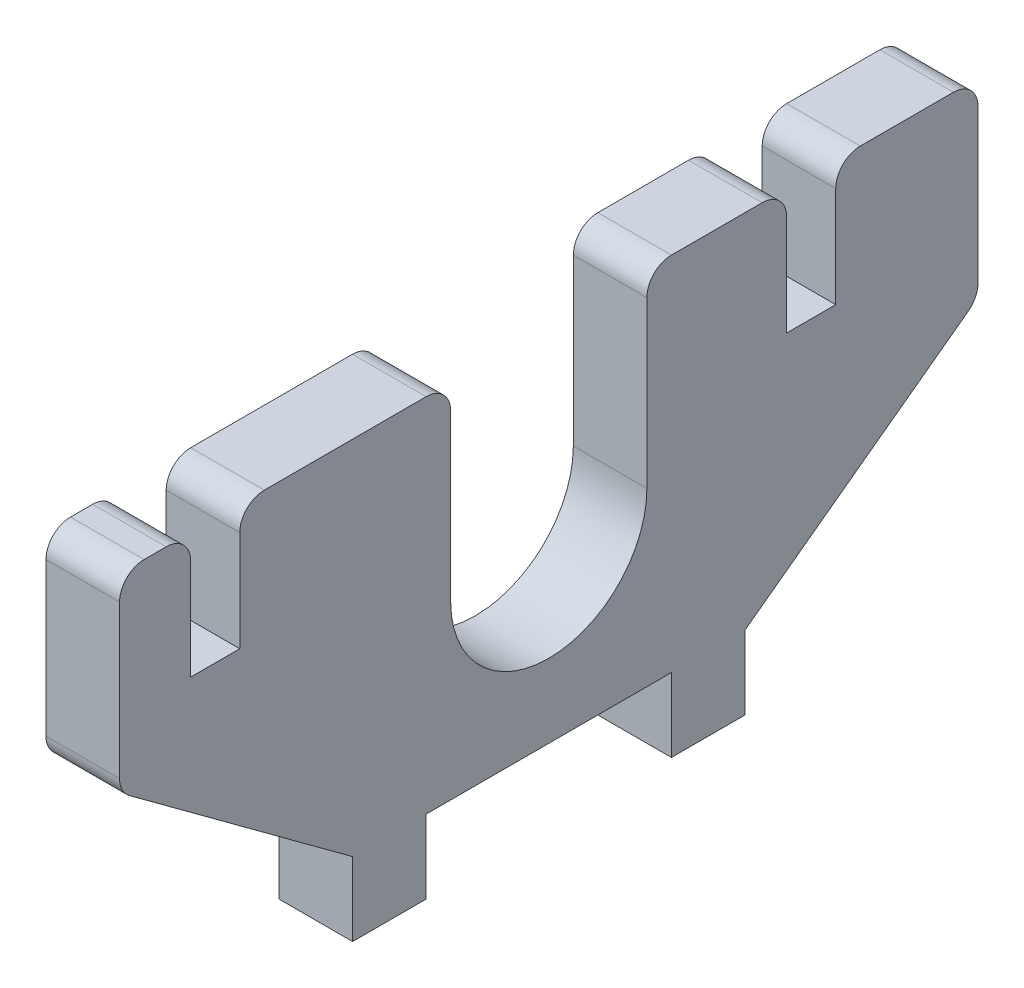
SolidWorks part; units mm, degrees
ref_plane "Front Plane" through (0, 0, 0) normal (0, 0, 1) x (1, 0, 0)
ref_plane "Top Plane" through (0, 0, 0) normal (0, 1, 0) x (1, 0, 0)
ref_plane "Right Plane" through (0, 0, 0) normal (1, 0, 0) x (0, 0, -1)
sketch "Sketch1" plane through (0, 0, 0) normal (0, 1, 0) x (1, 0, 0)
  line L0 (-450, 300) -> (-400, 300)
  line L1 (-400, 300) -> (-200, 250)
  line L2 (-200, 250) -> (200, 250) construction
  line L3 (200, 250) -> (600, 40) construction
  line L4 (600, 40) -> (1200, 40)
  line L5 (-450, -300) -> (-400, -300)
  line L6 (-400, -300) -> (-200, -250)
  line L7 (-200, -250) -> (200, -250) construction
  line L8 (200, -250) -> (600, -40) construction
  line L9 (600, -40) -> (1200, -40)
  line L10 (600, 40) -> (600, -40) construction
  line L11 (200, -250) -> (200, 250) construction
  line L12 (-200, 250) -> (-200, -250) construction
  line L13 (-400, -300) -> (-400, 300) construction
  line L14 (0, 0) -> (200, 0) construction
  line L15 (0, 250) -> (0, 0) construction
  line L16 (1200, 40) -> (1200, -40)
  line L17 (-450, 300) -> (-450, -300)
  line L18 (600, 0) -> (200, 0) construction
  line L19 (-450, 0) -> (-400, 0) construction
  line L20 (-400, 0) -> (-200, 0) construction
  line L21 (-200, 0) -> (0, 0) construction
  line L22 (-200, 250) -> (600, 40)
  line L23 (600, -40) -> (-200, -250)
  dimension "D1" = 600
  dimension "D2" = 200
  dimension "D3" = 50
  dimension "D4" = 400
  dimension "D5" = 500
  dimension "D6" = 80
  dimension "D7" = 600
  dimension "D8" = 400
extrude "Boss-Extrude1" add sketch "Sketch1" along normal blind 15
sketch "Sketch2" plane through (0, 0, 0) normal (0, 0, 1) x (1, 0, 0)
  line L0 (-450, 0) -> (-450, -40)
  line L1 (-450, -40) -> (-400, -40)
  line L2 (-400, -40) -> (-400, 0)
  line L3 (-400, 0) -> (-200, 0) construction
  line L4 (-400, 0) -> (-450, 0)
  line L5 (-440, -15) -> (-440, -40)
  line L6 (-410, -15) -> (-410, -40)
  line L7 (-425, 0) -> (-425, -15) construction
  circle A0 centre (-425, -15) radius 15
  dimension "D1" = 30
  dimension "D2" = 40
extrude "Boss-Extrude2" add sketch "Sketch2" along normal up to surface and the other way up to surface contours L4 L7 A0 L6 L1 L2 | L7 L4 L0 L1 L5 A0 up to face at (-425, 7.5, 300) other way up to face at (-425, 7.5, -300)
sketch "Sketch4" plane through (0, 0, 0) normal (0, 1, 0) x (1, 0, 0)
  line L0 (-450, 230) -> (-400, 230)
  line L1 (-450, 300) -> (-450, -300) construction
  line L2 (-400, 230) -> (-150, 167.5)
  line L3 (-150, 167.5) -> (-150, -167.5)
  line L4 (-150, -167.5) -> (-400, -230)
  line L5 (-400, -230) -> (-450, -230)
  line L6 (-400, 230) -> (-400, -230) construction
  line L7 (-200, 250) -> (-200, -250) construction
  line L9 (-200, 0) -> (-150, 0) construction
  line L10 (-400, -230) -> (-400, -300) construction
  line L11 (-400, -300) -> (-200, -250) construction
  line L12 (-450, 230) -> (-450, -230)
  line L14 (-200, 250) -> (-400, 300) construction
  line L15 (-100, 155) -> (-100, -155)
  line L16 (-100, -155) -> (520, 0)
  line L17 (520, 0) -> (-100, 155)
  line L18 (520, 0) -> (-100, 0) construction
  dimension "D1" = 460
  dimension "D2" = 300
  dimension "D3" = 50
extrude "Cut-Extrude2" cut sketch "Sketch4" against normal through all both and the other way through all
sketch "Sketch5" plane through (0, 0, 0) normal (1, 0, 0) x (0, 0, -1)
  line L0 (-300, 0) -> (-230, 0) construction
  line L1 (-285, 0) -> (-245, 0)
  line L2 (-285, 0) -> (-285, -40)
  line L3 (-285, -40) -> (-245, -40)
  line L4 (-245, 0) -> (-245, -40)
  line L5 (-300, -40) -> (-230, -40) construction
  line L6 (230, 0) -> (300, 0) construction
  line L7 (245, 0) -> (285, 0)
  line L8 (245, 0) -> (245, -40)
  line L9 (245, -40) -> (285, -40)
  line L10 (285, 0) -> (285, -40)
  line L11 (230, -40) -> (300, -40) construction
  line L12 (-300, 0) -> (-300, -40) construction
  line L13 (230, -40) -> (230, 0) construction
  line L14 (300, 0) -> (300, -40) construction
  dimension "D1" = 15
  dimension "D2" = 15
  dimension "D3" = 15
  dimension "D4" = 15
extrude "Cut-Extrude3" cut sketch "Sketch5" against normal through all
sketch "Sketch7" plane through (1200, 0, 0) normal (1, 0, 0) x (0, 0, -1)
  line L1 (-40, 15) -> (-87.5, 50)
  line L2 (-87.5, 50) -> (-87.5, 88.7)
  line L3 (-87.5, 88.7) -> (87.5, 88.7)
  line L4 (87.5, 88.7) -> (87.5, 50)
  line L5 (87.5, 50) -> (40, 15)
  line L7 (-40, 15) -> (40, 15)
  line L8 (-20, 50) -> (-20, 88.7)
  line L9 (87.5, 50) -> (-87.5, 50) construction
  line L10 (0, 88.7) -> (0, 50) construction
  line L11 (-20, 88.7) -> (20, 88.7)
  line L12 (0, 50) -> (0, 0) construction
  line L13 (20, 88.7) -> (20, 50)
  line L14 (-73, 88.7) -> (-63, 88.7)
  line L15 (-73, 88.7) -> (-73, 63.2)
  line L16 (-73, 63.2) -> (-63, 63.2)
  line L17 (-63, 88.7) -> (-63, 63.2)
  line L18 (48.5, 88.7) -> (58.5, 88.7)
  line L19 (48.5, 88.7) -> (48.5, 63.2)
  line L20 (48.5, 63.2) -> (58.5, 63.2)
  line L21 (58.5, 88.7) -> (58.5, 63.2)
  circle A0 centre (0, 50) radius 20
  dimension "D3" = 40
  dimension "D1" = 175
  dimension "D2" = 50
  dimension "D4" = 25.5
  dimension "D5" = 10
  dimension "D6" = 63
  dimension "D7" = 48.5
  dimension "D8" = 38.7
extrude "Boss-Extrude4" add sketch "Sketch7" against normal blind 75
sketch "Sketch8" plane through (0, 0, 0) normal (0, 0, 1) x (1, 0, 0)
  line L0 (1125, 88.7) -> (1200, 88.7) construction
  line L1 (1140, 88.7) -> (1185, 88.7)
  line L2 (1140, 88.7) -> (1140, 15)
  line L3 (1140, 15) -> (1185, 15)
  line L4 (1185, 88.7) -> (1185, 15)
  line L5 (1125, 15) -> (1200, 15) construction
  line L6 (1125, 50) -> (1125, 88.7) construction
  line L7 (1200, 50) -> (1200, 88.7) construction
  line L8 (1155, 88.7) -> (1170, 88.7) construction
  line L9 (1155, 88.7) -> (1170, 88.7)
  line L10 (1155, 88.7) -> (1155, 15)
  line L11 (1155, 15) -> (1170, 15)
  line L12 (1170, 88.7) -> (1170, 15)
  line L15 (1162.5, 50) -> (1162.5, 88.7) construction
  line L16 (1125, 50) -> (1200, 50) construction
  line L17 (1155, 88.7) -> (1170, 88.7) construction
  dimension "D1" = 15
  dimension "D2" = 15
  dimension "D3" = 15
extrude "Cut-Extrude4" cut sketch "Sketch8" against normal through all both and the other way through all contours L10 L1 L2 L3 | L1 L12 L3 L4
fillet "Fillet1" radius 5 53 edges at (1192.5, 50, 87.5) (1162.5, 50, 87.5) (1132.5, 50, 87.5) (1192.5, 50, -87.5) (1162.5, 50, -87.5) (1132.5, 50, -87.5) (1192.5, 88.7, -87.5) (1162.5, 88.7, -87.5) (1132.5, 88.7, -87.5) (1132.5, 88.7, -58.5) (1162.5, 88.7, -58.5) (1192.5, 88.7, -58.5) (1192.5, 88.7, -48.5) (1162.5, 88.7, -48.5) (1132.5, 88.7, -48.5) (1192.5, 88.7, -20) (1162.5, 88.7, -20) (1132.5, 88.7, -20) (1192.5, 88.7, 63) (1162.5, 88.7, 63) (1132.5, 88.7, 63) (1132.5, 88.7, 87.5) (1162.5, 88.7, 87.5) (1192.5, 88.7, 87.5) (1192.5, 88.7, 73) (1162.5, 88.7, 73) (1132.5, 88.7, 73) (1192.5, 88.7, 20) (1162.5, 88.7, 20) (1132.5, 88.7, 20) (600, 7.5, 40) (600, 7.5, -40) (520, 7.5, 0) (-440, -40, -292.5) (-440, -40, -237.5) (-400, -40, -292.5) (-400, -40, -237.5) (-450, -40, -237.5) (-410, -40, -237.5) (-450, -40, -292.5) (-410, -40, -292.5) (-150, 7.5, 167.5) (-100, 7.5, 155) (-150, 7.5, -167.5) (-100, 7.5, -155) (-450, -40, 237.5) (-410, -40, 237.5) (-440, -40, 237.5) (-400, -40, 237.5) (-450, -40, 292.5) (-440, -40, 292.5) (-400, -40, 292.5) (-410, -40, 292.5)
sketch "Sketch9" plane through (0, 0, 0) normal (0, 1, 0) x (1, 0, 0)
  line L0 (1185, 87.5) -> (1185, 82.5) construction
  line L1 (-450, 300) -> (1185, 300)
  line L2 (-450, 300) -> (-450, -300)
  line L3 (-450, -300) -> (1185, -300)
  line L4 (1185, 300) -> (1185, -300)
  point P5 (-450, -300)
extrude "Cut-Extrude5" cut sketch "Sketch9" against normal through all both and the other way through all
sketch "Sketch10" plane through (1200, 0, 0) normal (1, 0, 0) x (0, 0, -1)
  line L0 (-40, 0) -> (40, 0) construction
  line L1 (-25, 0) -> (25, 0)
  line L2 (-25, 0) -> (-25, 15)
  line L3 (-25, 15) -> (25, 15)
  line L4 (25, 0) -> (25, 15)
  line L5 (0, 15) -> (0, 0) construction
  line L6 (-40, 15) -> (-40, 0) construction
  dimension "D1" = 15
  dimension "D2" = 15
extrude "Cut-Extrude6" cut sketch "Sketch10" against normal through all
